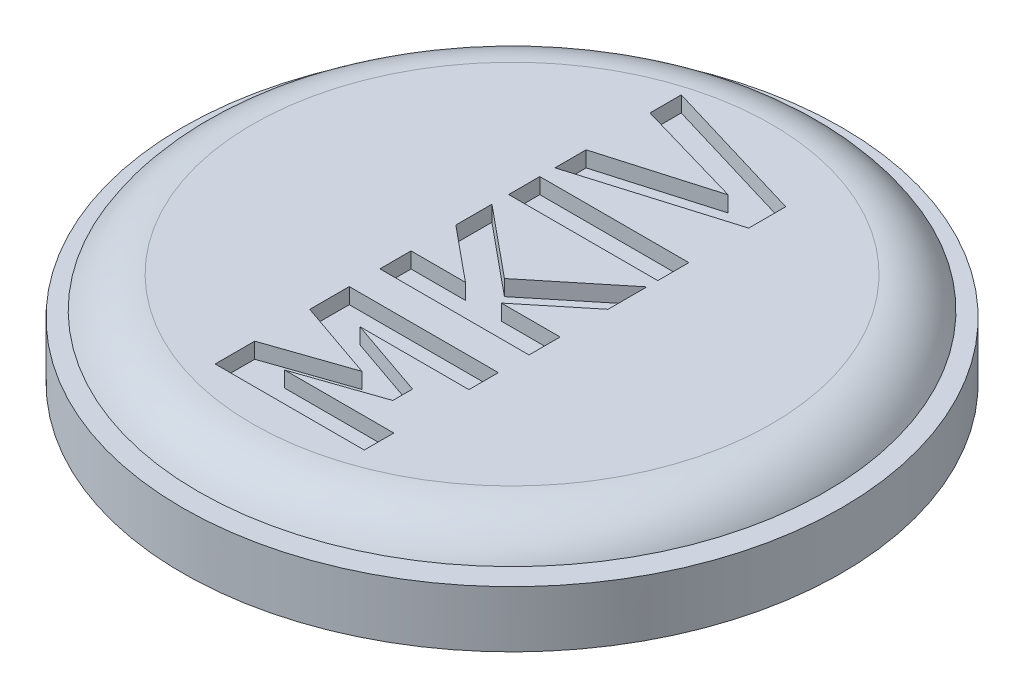
SolidWorks part; units mm, degrees
ref_plane "Спереди" through (0, 0, 0) normal (0, 0, 1) x (1, 0, 0)
ref_plane "Сверху" through (0, 0, 0) normal (0, 1, 0) x (1, 0, 0)
ref_plane "Справа" through (0, 0, 0) normal (1, 0, 0) x (0, 0, -1)
sketch "Sketch1" plane through (0, 0, 0) normal (0, 1, 0) x (1, 0, 0)
  circle A0 centre (0, 0) radius 17.4
  dimension "D1" = 34.8
extrude "Boss-Extrude1" add sketch "Sketch1" along normal blind 4
sketch "Sketch2" plane through (0, 4, 0) normal (0, 1, 0) x (1, 0, 0)
  circle A0 centre (0, 0) radius 20
  dimension "D1" = 40
extrude "Boss-Extrude2" add sketch "Sketch2" along normal blind 2
chamfer "Chamfer1" distance 0.5 angle 70 1 edges at (0, 0, 17.4) first distance on face at (0, 0, 17.4)
sketch "Sketch3" plane through (0, 6, 0) normal (0, 1, 0) x (1, 0, 0)
  line L0 (5, -19.3649) -> (5, 19.3649) construction
  line L1 (0, -20) -> (0, 20) construction
  circle A0 centre (0, 0) radius 20 construction
  text T0 "MKIV" font "DejaVu Sans Condensed" height 9.5
  dimension "D1" = 5
sketch "Sketch4" plane through (0, 0, 0) normal (0, -1, 0) x (1, 0, 0)
  circle A0 centre (0, 0) radius 17.9
  circle A1 centre (0, 0) radius 21
  circle A2 centre (0, 0) radius 16.9 construction
  circle A3 centre (0, 0) radius 20 construction
  dimension "D1" = 1
  dimension "D2" = 1
extrude "Boss-Extrude4" add sketch "Sketch4" against normal offset from surface (3.6 mm away) 0.4 separate body up to face at (0, 4, 17.4)
fillet "Fillet1" radius 4 1 edges at (0, 6, 20)
extrude "Cut-Extrude1" cut sketch "Sketch3" against normal blind 1
sketch "Sketch5" plane through (0, 0, 0) normal (0, -1, 0) x (1, 0, 0)
  circle A0 centre (0, 0) radius 14.8
  circle A1 centre (0, 0) radius 17.4 construction
  dimension "D1" = 2.6
extrude "Cut-Extrude2" cut sketch "Sketch5" against normal up to surface (4 mm away) up to face at (0, 4, 17.4)
